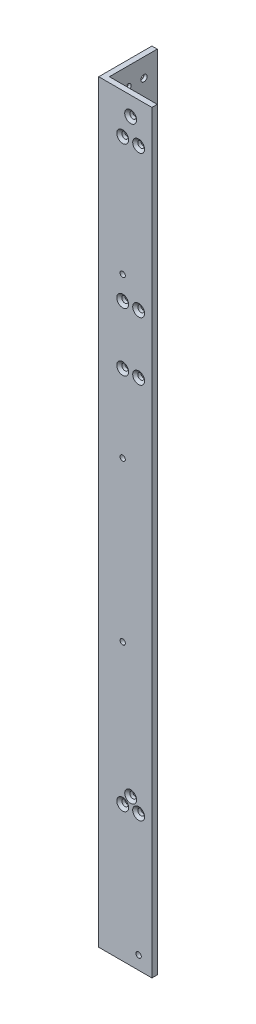
SolidWorks part; units mm, degrees
ref_plane "Front Plane" through (0, 0, 0) normal (0, 0, 1) x (1, 0, 0)
ref_plane "Top Plane" through (0, 0, 0) normal (0, 1, 0) x (1, 0, 0)
ref_plane "Right Plane" through (0, 0, 0) normal (1, 0, 0) x (0, 0, -1)
sketch "Sketch2" plane through (0, 0, 0) normal (0, 1, 0) x (1, 0, 0)
  line L0 (0, 31.75) -> (3.175, 31.75)
  line L1 (3.175, 31.75) -> (3.175, 3.175)
  line L2 (3.175, 3.175) -> (31.75, 3.175)
  line L3 (31.75, 3.175) -> (31.75, 0)
  line L4 (31.75, 0) -> (0, 0)
  line L5 (0, 0) -> (0, 31.75)
  point P9 (1.5875, 31.75)
  point P10 (31.75, 1.5875)
  dimension "D4" = 3.175
  dimension "D1" = 31.75
  dimension "D2" = 31.75
  dimension "D3" = 3.175
extrude "Boss-Extrude1" add sketch "Sketch2" along normal blind 450
sketch "LeftSideHoles-Sketch3" plane through (0, 0, 0) normal (0, 0, 1) x (1, 0, 0)
  line L0 (0, 0) -> (31.75, 0) construction
  line L1 (0, 450) -> (31.75, 450) construction
  line L3 (0, 450) -> (0, 0) construction
  circle A0 centre (14.2875, 81.1125) radius 1.5875
  circle A1 centre (23.8125, 81.1125) radius 1.5875
  circle A3 centre (19.05, 87.4625) radius 1.5875
  circle A5 centre (14.2875, 426.1875) radius 1.5875
  circle A6 centre (19.05, 438.8875) radius 1.5875
  circle A7 centre (23.8125, 426.1875) radius 1.5875
  circle A10 centre (14.2875, 341.2474) radius 1.5875
  circle A11 centre (23.8125, 341.2474) radius 1.5875
  circle A12 centre (14.2875, 306.3224) radius 1.5875
  circle A13 centre (23.8125, 306.3224) radius 1.5875
  circle A15 centre (23.8125, 7.9375) radius 1.5875
  circle A16 centre (14.2875, 165) radius 1.5875
  circle A17 centre (14.2875, 260) radius 1.5875
  circle A18 centre (14.2875, 355) radius 1.5875
  point P24 (15.875, 0)
  dimension "D4" = 3.175
  dimension "D1" = 81.1125
  dimension "D2" = 14.2875
  dimension "D7" = 34.925
  dimension "D11" = 341.2474
  dimension "D12" = 165
  dimension "D13" = 95
  dimension "D5" = 6.35
  dimension "D6" = 12.7
  dimension "D8" = 11.1125
  dimension "D9" = 95
  dimension "D14" = 19.05
  dimension "D3" = 23.8125
  dimension "D10" = 7.9375
sketch "BackSideHoles-Sketch4" plane through (0, 0, 0) normal (-1, 0, 0) x (0, 0, 1)
  line L0 (-31.75, 450) -> (0, 450) construction
  line L2 (0, 450) -> (0, 0) construction
  line L3 (-31.75, 0) -> (0, 0) construction
  circle A0 centre (-19.05, 81.1125) radius 1.5875
  circle A2 centre (-23.8125, 87.4625) radius 1.5875
  circle A3 centre (-14.2875, 87.4625) radius 1.5875
  circle A4 centre (-23.8125, 438.8875) radius 1.5875
  circle A5 centre (-14.2875, 438.8875) radius 1.5875
  circle A6 centre (-19.05, 426.1875) radius 1.5875
  circle A10 centre (-23.8125, 336.7474) radius 1.5875
  circle A11 centre (-14.2875, 336.7474) radius 1.5875
  circle A12 centre (-19.05, 330.3974) radius 1.5875
  circle A14 centre (-14.2875, 165) radius 1.5875
  circle A15 centre (-14.2875, 260) radius 1.5875
  circle A17 centre (-23.8125, 7.9375) radius 1.5875
  circle A19 centre (-14.2875, 355) radius 1.5875
  dimension "D4" = 3.175
  dimension "D2" = 14.2875
  dimension "D5" = 6.35
  dimension "D14" = 19.05
  dimension "D6" = 11.1125
  dimension "D8" = 6.35
  dimension "D7" = 12.7
  dimension "D1" = 336.7474
  dimension "D10" = 165
  dimension "D11" = 95
  dimension "D13" = 7.9375
  dimension "D3" = 81.1125
  dimension "D12" = 95
  dimension "D9" = 23.8125
extrude "LeftSideHoles-Cut-Extrude1" cut sketch "LeftSideHoles-Sketch3" against normal blind 3.175
extrude "BackSideHoles-Cut-Extrude2" cut sketch "BackSideHoles-Sketch4" against normal blind 3.175
sketch "Sketch5" plane through (0, 0, 0) normal (-1, 0, 0) x (0, 0, 1)
  point P0 (-14.2875, 438.8875)
  point P3 (-23.8125, 438.8875)
  point P6 (-19.05, 426.1875)
  point P9 (-19.05, 330.3974)
  point P12 (-14.2875, 336.7474)
  point P15 (-23.8125, 336.7474)
  point P18 (-19.05, 81.1125)
  point P21 (-14.2875, 87.4625)
  point P24 (-23.8125, 87.4625)
hole_wizard "CSK for #6 Flat Head Machine Screw (100)1" positions "Sketch5" profile "Sketch6" countersink size "#6" standard "ANSI Inch" end condition through all
sketch "Sketch6" plane through (0, 438.8875, -14.2875) normal (0, 1, 0) x (0, 0, 1)
  line L0 (0, 0) -> (0, 31.75)
  line L1 (0, 31.75) -> (1.8986, 31.75)
  line L2 (1.8986, 31.75) -> (1.8986, 1.38)
  line L3 (1.8986, 1.38) -> (3.5433, 0)
  line L5 (3.5433, 0) -> (0, 0)
  line L6 (-1.8986, 1.38) -> (-3.5433, 0) construction
  line L11 (0, -6.35) -> (0, 107.95) construction
  dimension "Thru Hole Dia." = 3.7973
  dimension "Thru Hole Depth" = 31.75
  dimension "Near C'Sink Dia." = 7.0866
  dimension "Near C'Sink Angle" = 100
sketch "Sketch8" plane through (0, 0, 0) normal (0, 0, 1) x (1, 0, 0)
  point P0 (19.05, 438.8875)
  point P3 (14.2875, 426.1875)
  point P6 (23.8125, 426.1875)
  point P9 (23.8125, 341.2474)
  point P12 (14.2875, 341.2474)
  point P15 (14.2875, 306.3224)
  point P18 (23.8125, 306.3224)
  point P21 (19.05, 87.4625)
  point P24 (14.2875, 81.1125)
  point P27 (23.8125, 81.1125)
hole_wizard "CSK for #6 Flat Head Machine Screw (100)2" positions "Sketch8" profile "Sketch9" countersink size "#6" standard "ANSI Inch" end condition through all
sketch "Sketch9" plane through (19.05, 438.8875, 0) normal (1, 0, 0) x (0, -1, 0)
  line L0 (0, 0) -> (0, 31.75)
  line L1 (0, 31.75) -> (1.8986, 31.75)
  line L2 (1.8986, 31.75) -> (1.8986, 1.38)
  line L3 (1.8986, 1.38) -> (3.5433, 0)
  line L5 (3.5433, 0) -> (0, 0)
  line L6 (-1.8986, 1.38) -> (-3.5433, 0) construction
  line L11 (0, -6.35) -> (0, 107.95) construction
  dimension "Thru Hole Dia." = 3.7973
  dimension "Thru Hole Depth" = 31.75
  dimension "Near C'Sink Dia." = 7.0866
  dimension "Near C'Sink Angle" = 100
equation "\"RailThickness\"= .125in'Spec"
equation "\"VSWidth\"= 1.25in'Spec"
equation "\"VSHeight\"= 1.25in'Spec"
equation "\"VSLength\"= 450mm"
equation "\"HoleOffsetFromEdge\"= \"RailThickness\" * 2.5"
equation "\"HoleOffsetFromSide\"= \"RailThickness\" * 3.5"
equation "\"LegHeight\"= 70mm'Space needed for PSU/Stepper/Electronics"
equation "\"VSBottomSideRailHoleY1FromBottomOfLowerRail\"= \"V1 BottomOfLowerRail\" + \"HoleOffsetFromSide\"'Equals 81.1125"
equation "\"VSSideRailHoleX1FromSide\"= \"HoleOffsetFromSide\" + \"RailThickness\""
equation "\"FasteningHoleDiameter\"= .125in"
equation "\"VSBottomSideRailHoleY2FromY1\"= \"LowerRailHeight\" - \"HoleOffsetFromSide\" - \"HoleOffsetFromEdge\"'Equals 6.35"
equation "\"VSTopSideRailHoleY1FromEdge\"= \"HoleOffsetFromEdge\" + \"RailThickness\""
equation "\"D4@LeftSideHoles-Sketch3\"=\"FasteningHoleDiameter\""
equation "\"D1@LeftSideHoles-Sketch3\"=\"VSBottomSideRailHoleY1FromBottomOfLowerRail\""
equation "\"D2@LeftSideHoles-Sketch3\"=\"VSSideRailHoleX1FromSide\""
equation "\"D1@Boss-Extrude1\"=\"VSLength\""
equation "\"D4@BackSideHoles-Sketch4\" = \"FasteningHoleDiameter\""
equation "\"VSMidSideRailHoleY1FromV8TopOfMidSideRail\"= \"V8 ToTopOfMidSideRail\" - \"HoleOffsetFromEdge\"'Equals 341.24737"
equation "\"LowerRailHeight\"= 1.00in"
equation "\"D1@Sketch2\"=\"VSHeight\""
equation "\"D2@Sketch2\"=\"VSWidth\""
equation "\"MidBackRailHeight\"= 1.00in"
equation "\"VSMidBackRailHoleY1FromV7TopOfMidBackRail\"= \"V7 ToTopOfMidBackRail\" - \"HoleOffsetFromEdge\"'Equals 339.64737"
equation "\"TopRailHeight\"= 1.25in"
equation "\"MidLeftOrRightSideRailHeight\"= 2.0in"
equation "\"VSMidBackRailHoleY2FromY1\"= \"MidBackRailHeight\" - \"HoleOffsetFromSide\" - \"HoleOffsetFromEdge\"'Equals 6.35"
equation "\"VSMidSideRailHoleY2FromY1\"= \"MidLeftOrRightSideRailHeight\" - \"HoleOffsetFromEdge\" * 2'Equals 34.925"
equation "\"D7@LeftSideHoles-Sketch3\"=\"VSMidSideRailHoleY2FromY1\""
equation "\"D8@BackSideHoles-Sketch4\"=\"VSMidBackRailHoleY2FromY1\""
equation "\"D6@BackSideHoles-Sketch4\"=\"VSTopSideRailHoleY1FromEdge\""
equation "\"VSTopSideRailHoleY2FromY1\"= \"TopRailHeight\" - \"VSTopSideRailHoleY1FromEdge\" - \"HoleOffsetFromEdge\"'Equals 12.7"
equation "\"D7@BackSideHoles-Sketch4\"=\"VSTopSideRailHoleY2FromY1\""
equation "\"VSSideRailHoleX2FromSide\"= \"VSWidth\" - \"HoleOffsetFromEdge\""
equation "\"V1 BottomOfLowerRail\"= \"LegHeight\""
equation "\"StepperShaftLength\"= 24mm'Pulley will be attached to the end"
equation "\"ZAxisLeadScrewLength\"= 200mm"
equation "\"LM8UUHeight\"= 24mm'Spec"
equation "\"V2 ToBedAtTopOfZAxis\"= \"V1 BottomOfLowerRail\" - \"LowerEnclosureThickness\" + \"StepperShaftLength\" + \"ZAxisLeadScrewLength\" - \"LM8UUHeight\" / 2'Equals 277"
equation "\"HotEndToTopOfXAxisGB\"= 71.68487mm'Equals 71.68487. Measured after installed onto X-Axis linear rail guide block"
equation "\"TopOfGBToBottomOfLinearRail\"= \"LinearGBWidth\" / 2 + \"LinearRailWidth\" / 2'Equals 19.5"
equation "\"LinearGBWidth\"= 27mm'Spec"
equation "\"V5 ToBottomOfXAxisLinearRail\"= \"V4 ToTopOfBuildPlate/HotEndTip\" + \"HotEndToTopOfXAxisGB\" - \"TopOfGBToBottomOfLinearRail\"'Equals 352.18487"
equation "\"LinearRailWidth\"= 12mm'Spec"
equation "\"GABUpperHeight\"= 4mm"
equation "\"GABMidWallHeight\"= 28mm'Must equal 28 or changes alignment"
equation "\"V7 ToBottomOfMidBackRail\"=   \"V5 ToBottomOfXAxisLinearRail\" - \"GABUpperHeight\" - \"GABMidShortRiserHeight\" + \"GABRiserBossOffset\" - \"StepperShaftLength\"'Equals 319.28487"
equation "\"D1@BackSideHoles-Sketch4\" = \"VSMidBackRailHoleY1FromV7TopOfMidBackRail\""
equation "\"D11@LeftSideHoles-Sketch3\"=\"VSMidSideRailHoleY1FromV8TopOfMidSideRail\""
equation "\"V4 ToTopOfBuildPlate/HotEndTip\"= \"V2 ToBedAtTopOfZAxis\" + \"BedToBuildPlateStandoffLength\" + \"BuildPlateHeight\""
equation "\"BedToBuildPlateStandoffLength\"= 15mm"
equation "\"BuildPlateHeight\"= 8mm'Spec"
equation "\"V8 ToTopOfMidSideRail\"= \"V6 ToMiddleOfYAxisGantryBlock\" + \"MidSideRailVerticalOffset\"'Equals 349.18487"
equation "\"VSEnclosureOffsets\"= ( \"VSLength\" - \"LegHeight\" ) / 4"
equation "\"D12@LeftSideHoles-Sketch3\"=\"LegHeight\" + \"VSEnclosureOffsets\""
equation "\"D13@LeftSideHoles-Sketch3\"=\"VSEnclosureOffsets\""
equation "\"D10@BackSideHoles-Sketch4\"=\"LegHeight\" + \"VSEnclosureOffsets\""
equation "\"D11@BackSideHoles-Sketch4\"=\"VSEnclosureOffsets\""
equation "\"D13@BackSideHoles-Sketch4\"=\"HoleOffsetFromEdge\""
equation "\"D5@BackSideHoles-Sketch4\"=\"VSBottomSideRailHoleY2FromY1\""
equation "\"D3@BackSideHoles-Sketch4\"=\"VSBottomSideRailHoleY1FromBottomOfLowerRail\""
equation "\"D2@BackSideHoles-Sketch4\"=\"VSSideRailHoleX1FromSide\""
equation "\"D5@LeftSideHoles-Sketch3\"=\"VSBottomSideRailHoleY2FromY1\""
equation "\"D6@LeftSideHoles-Sketch3\"=\"VSTopSideRailHoleY2FromY1\""
equation "\"D8@LeftSideHoles-Sketch3\"=\"VSTopSideRailHoleY1FromEdge\""
equation "\"LowerEnclosureThickness\"= 5mm"
equation "\"V7 ToTopOfMidBackRail\"= \"V7 ToBottomOfMidBackRail\" + \"MidBackRailHeight\""
equation "\"GABHeight\"= \"GABLowerHeight\" + \"GABMidWallHeight\" + \"GABUpperHeight\""
equation "\"GABLowerHeight\"= 4mm"
equation "\"V6 ToMiddleOfYAxisGantryBlock\"= \"V5 ToBottomOfXAxisLinearRail\" - \"GABHeight\" / 2'Equals 334.18487"
equation "\"D9@LeftSideHoles-Sketch3\"=\"VSEnclosureOffsets\""
equation "\"D12@BackSideHoles-Sketch4\"=\"VSEnclosureOffsets\""
equation "\"MidSideRailVerticalOffset\"= \"LinearRailWidth\" + 3mm'Allows space for RodStabilizer to attach to bottom of MidSideRail"
equation "\"GABRiserBossOffset\"= 0.4mm'Aligns Pulleys inside edges to be 2.5mm (.5mm apart top to bottom)"
equation "\"GABMidShortRiserHeight\"= \"GABMidWallHeight\" / 2 - \"20TGT2PulleyWidth\"'Equals 5.3"
equation "\"20TGT2PulleyWidth\"= 8.7mm'The STL of the Pulley in the diagram is a bit larger"
equation "\"VSMidSideRailHoleXFromSideToCenter\"= \"RailThickness\" * 6"
equation "\"D14@LeftSideHoles-Sketch3\"=\"VSMidSideRailHoleXFromSideToCenter\""
equation "\"D14@BackSideHoles-Sketch4\"=\"VSMidSideRailHoleXFromSideToCenter\""
equation "\"D10@LeftSideHoles-Sketch3\"=\"HoleOffsetFromEdge\""
equation "\"D3@LeftSideHoles-Sketch3\"=\"VSSideRailHoleX2FromSide\""
equation "\"D9@BackSideHoles-Sketch4\"=\"VSSideRailHoleX2FromSide\""
